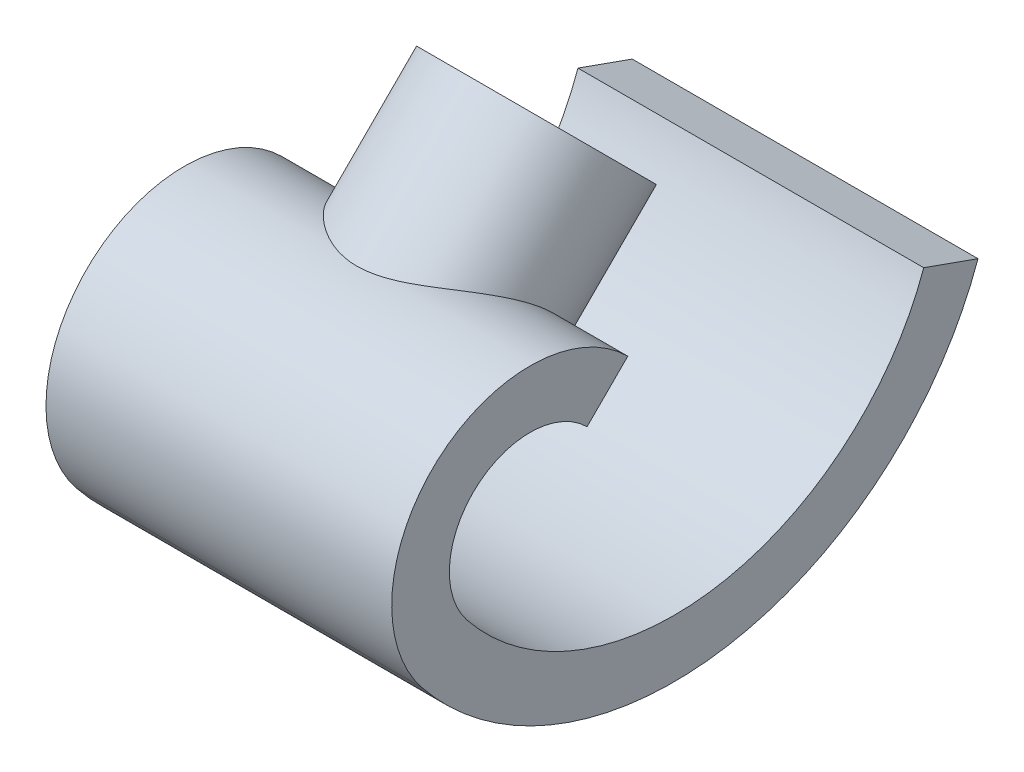
SolidWorks part; units mm, degrees
ref_plane "Спереди" through (0, 0, 0) normal (0, 0, 1) x (1, 0, 0)
ref_plane "Сверху" through (0, 0, 0) normal (0, 1, 0) x (1, 0, 0)
ref_plane "Справа" through (0, 0, 0) normal (1, 0, 0) x (0, 0, -1)
sketch "Sketch1" plane through (0, 0, 0) normal (1, 0, 0) x (0, 0, -1)
  line L0 (-4.0047, 8.4853) -> (-12.49, 0) construction
  line L1 (-12.49, 0) -> (-12.49, 19.5798) construction
  arc A0 (-21.8575, -7.5) -> (26.3823, 0.6205) centre (0, 10) ccw
  arc A1 (-21.8575, -7.5) -> (-4.0047, 8.4853) centre (-12.49, 0) cw
  dimension "D1" = 28
  dimension "D3" = 12
  dimension "D2" = 10
  dimension "D4" = 45
extrude "Extrude-Thin1" add sketch "Sketch1" along normal mid plane 30 thin thin type one direction wall 5
sketch "Sketch2" plane through (0, 0, 0) normal (1, 0, 0) x (0, 0, -1)
  line L0 (-12.49, 0) -> (-4.0047, 8.4853) construction
  line L1 (-4.0047, 8.4853) -> (-12.0252, 16.5058) construction
ref_plane "Plane1" through (0, 2.2403, -2.2403) normal (0, 0.7071, -0.7071) x (1, 0, 0)
sketch "Sketch3" plane through (0, 2.2403, -2.2403) normal (0, 0.7071, -0.7071) x (1, 0, 0)
  line L0 (15, -8.8318) -> (-15, -8.8318) construction
  circle A0 centre (0, -8.8318) radius 4.5
  circle A1 centre (0, -8.8318) radius 8.5
  dimension "D1" = 9
  dimension "D2" = 4
extrude "Boss-Extrude1" add sketch "Sketch3" along normal blind 10 and the other way blind 4
